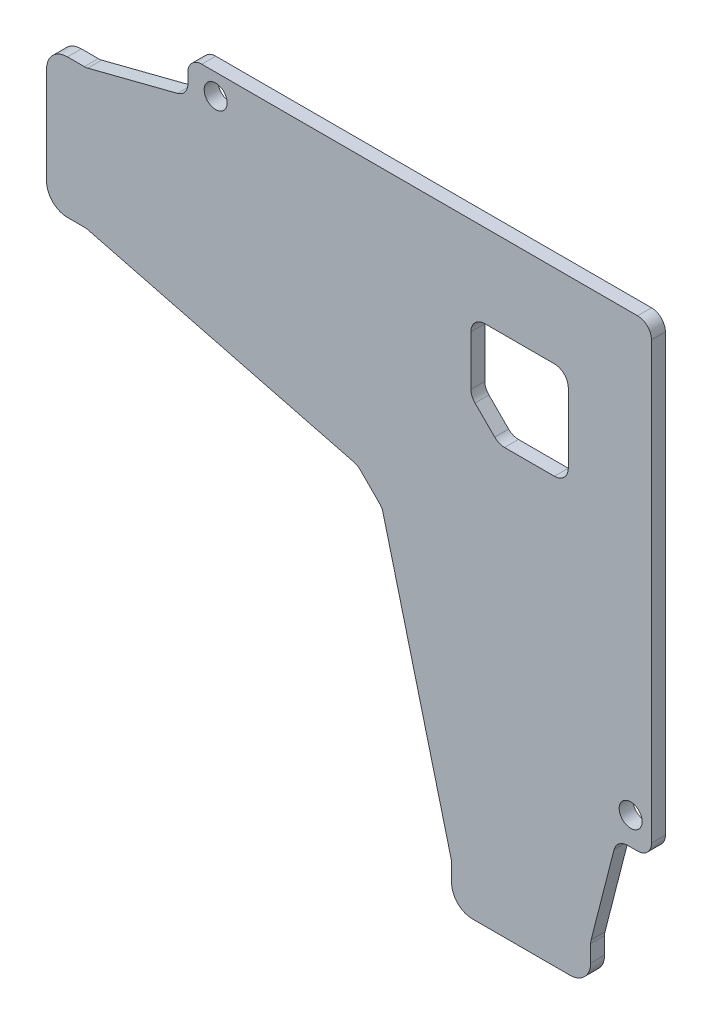
SolidWorks part; units mm, degrees
ref_plane "Front Plane" through (0, 0, 0) normal (0, 0, 1) x (1, 0, 0)
ref_plane "Top Plane" through (0, 0, 0) normal (0, 1, 0) x (1, 0, 0)
ref_plane "Right Plane" through (0, 0, 0) normal (1, 0, 0) x (0, 0, -1)
sketch "Sketch1" plane through (0, 0, 0) normal (0, 0, 1) x (1, 0, 0)
  line L0 (-86, -7.75) -> (-86, -27.75)
  line L1 (-27.75, -86) -> (-7.75, -86)
  line L2 (-86, -7.75) -> (-95.5, -7.75) construction
  line L3 (-86, -27.75) -> (-80.5674, -27.75)
  line L4 (-27.75, -86) -> (-27.75, -95.5) construction
  line L5 (-7.75, -86) -> (-7.75, -80.5674)
  line L23 (-10.25, -92) -> (-10.25, -95.5)
  line L24 (-10.25, -95.5) -> (-7.75, -95.5)
  line L25 (-7.75, -95.5) -> (-7.75, -80.5674)
  line L26 (-7.6874, -80.0709) -> (-4.3853, -67.1846)
  line L27 (-2.4479, -65.6811) -> (-1, -65.6811)
  line L28 (1, -63.6811) -> (1, -1)
  line L29 (-1, 1) -> (-63.6811, 1)
  line L30 (-65.6811, -1) -> (-65.6811, -2.4479)
  line L31 (-67.1846, -4.3853) -> (-80.0709, -7.6874)
  line L32 (-80.5674, -7.75) -> (-95.5, -7.75)
  line L33 (-95.5, -7.75) -> (-95.5, -10.25)
  line L34 (-95.5, -10.25) -> (-92, -10.25)
  line L35 (-90, -12.25) -> (-90, -23.25)
  line L36 (-92, -25.25) -> (-95.5, -25.25)
  line L37 (-95.5, -25.25) -> (-95.5, -27.75)
  line L38 (-95.5, -27.75) -> (-80.5674, -27.75)
  line L39 (-80.0709, -27.8126) -> (-41.8142, -37.6159)
  line L40 (-40.8965, -38.1391) -> (-38.1391, -40.8965)
  line L41 (-37.6159, -41.8142) -> (-27.8126, -80.0709)
  line L42 (-27.75, -80.5674) -> (-27.75, -95.5)
  line L43 (-27.75, -95.5) -> (-25.25, -95.5)
  line L44 (-25.25, -95.5) -> (-25.25, -92)
  line L45 (-23.25, -90) -> (-12.25, -90)
  line L46 (-10.25, -92) -> (-10.25, -95.5) construction
  line L47 (-10.25, -95.5) -> (-7.75, -95.5) construction
  line L48 (-7.75, -95.5) -> (-7.75, -86) construction
  line L49 (-7.6874, -80.0709) -> (-4.3853, -67.1846)
  line L50 (-2.4479, -65.6811) -> (-1, -65.6811)
  line L51 (1, -63.6811) -> (1, -1)
  line L52 (-1, 1) -> (-63.6811, 1)
  line L53 (-65.6811, -1) -> (-65.6811, -2.4479)
  line L54 (-67.1846, -4.3853) -> (-80.0709, -7.6874)
  line L55 (-80.5674, -7.75) -> (-86, -7.75)
  line L56 (-95.5, -7.75) -> (-95.5, -10.25) construction
  line L57 (-95.5, -10.25) -> (-92, -10.25) construction
  line L58 (-90, -12.25) -> (-90, -23.25) construction
  line L59 (-92, -25.25) -> (-95.5, -25.25) construction
  line L60 (-95.5, -25.25) -> (-95.5, -27.75) construction
  line L61 (-95.5, -27.75) -> (-86, -27.75) construction
  line L62 (-80.0709, -27.8126) -> (-41.8142, -37.6159)
  line L63 (-40.8965, -38.1391) -> (-38.1391, -40.8965)
  line L64 (-37.6159, -41.8142) -> (-27.8126, -80.0709)
  line L65 (-27.75, -80.5674) -> (-27.75, -86)
  line L66 (-27.75, -95.5) -> (-25.25, -95.5) construction
  line L67 (-25.25, -95.5) -> (-25.25, -92) construction
  line L68 (-23.25, -90) -> (-12.25, -90) construction
  arc A15 (-7.6874, -80.0709) -> (-7.75, -80.5674) centre (-5.75, -80.5674) ccw
  arc A16 (-2.4479, -65.6811) -> (-4.3853, -67.1846) centre (-2.4479, -67.6811) ccw
  arc A17 (-1, -65.6811) -> (1, -63.6811) centre (-1, -63.6811) ccw
  arc A18 (1, -1) -> (-1, 1) centre (-1, -1) ccw
  arc A19 (-63.6811, 1) -> (-65.6811, -1) centre (-63.6811, -1) ccw
  arc A20 (-67.1846, -4.3853) -> (-65.6811, -2.4479) centre (-67.6811, -2.4479) ccw
  arc A21 (-80.5674, -7.75) -> (-80.0709, -7.6874) centre (-80.5674, -5.75) ccw
  arc A22 (-90, -12.25) -> (-92, -10.25) centre (-92, -12.25) ccw
  arc A23 (-92, -25.25) -> (-90, -23.25) centre (-92, -23.25) ccw
  arc A24 (-80.0709, -27.8126) -> (-80.5674, -27.75) centre (-80.5674, -29.75) ccw
  arc A25 (-40.8965, -38.1391) -> (-41.8142, -37.6159) centre (-42.3107, -39.5533) ccw
  arc A26 (-37.6159, -41.8142) -> (-38.1391, -40.8965) centre (-39.5533, -42.3107) ccw
  arc A27 (-27.75, -80.5674) -> (-27.8126, -80.0709) centre (-29.75, -80.5674) ccw
  arc A28 (-23.25, -90) -> (-25.25, -92) centre (-23.25, -92) ccw
  arc A29 (-10.25, -92) -> (-12.25, -90) centre (-12.25, -92) ccw
  arc A30 (-7.6874, -80.0709) -> (-7.75, -80.5674) centre (-5.75, -80.5674) ccw
  arc A31 (-2.4479, -65.6811) -> (-4.3853, -67.1846) centre (-2.4479, -67.6811) ccw
  arc A32 (-1, -65.6811) -> (1, -63.6811) centre (-1, -63.6811) ccw
  arc A33 (1, -1) -> (-1, 1) centre (-1, -1) ccw
  arc A34 (-63.6811, 1) -> (-65.6811, -1) centre (-63.6811, -1) ccw
  arc A35 (-67.1846, -4.3853) -> (-65.6811, -2.4479) centre (-67.6811, -2.4479) ccw
  arc A36 (-80.5674, -7.75) -> (-80.0709, -7.6874) centre (-80.5674, -5.75) ccw
  arc A37 (-90, -12.25) -> (-92, -10.25) centre (-92, -12.25) ccw construction
  arc A38 (-92, -25.25) -> (-90, -23.25) centre (-92, -23.25) ccw construction
  arc A39 (-80.0709, -27.8126) -> (-80.5674, -27.75) centre (-80.5674, -29.75) ccw
  arc A40 (-40.8965, -38.1391) -> (-41.8142, -37.6159) centre (-42.3107, -39.5533) ccw
  arc A41 (-37.6159, -41.8142) -> (-38.1391, -40.8965) centre (-39.5533, -42.3107) ccw
  arc A42 (-27.75, -80.5674) -> (-27.8126, -80.0709) centre (-29.75, -80.5674) ccw
  arc A43 (-23.25, -90) -> (-25.25, -92) centre (-23.25, -92) ccw construction
  arc A44 (-10.25, -92) -> (-12.25, -90) centre (-12.25, -92) ccw construction
  dimension "D2" = 4
  dimension "D3" = 4
  dimension "D1" = 0
sketch "Sketch2" plane through (0, 0, 0) normal (0, 0, 1) x (1, 0, 0)
  circle A0 centre (-61.6811, -2) radius 1.65 construction
  circle A1 centre (-2, -61.6811) radius 1.65 construction
  circle A2 centre (-61.6811, -2) radius 1.65
  circle A3 centre (-2, -61.6811) radius 1.65
sketch "Sketch4" plane through (0, 0, 0) normal (0, 0, 1) x (1, 0, 0)
  line L0 (-24.9687, -12.9687) -> (-24.9687, -20.1403) construction
  line L1 (-12.9687, -10.9687) -> (-22.9687, -10.9687) construction
  line L2 (-10.9687, -22.9687) -> (-10.9687, -12.9687) construction
  line L3 (-20.1403, -24.9687) -> (-12.9687, -24.9687) construction
  line L4 (-24.9687, -12.9687) -> (-24.9687, -20.1403)
  line L5 (-12.9687, -10.9687) -> (-22.9687, -10.9687)
  line L6 (-10.9687, -22.9687) -> (-10.9687, -12.9687)
  line L7 (-20.1403, -24.9687) -> (-12.9687, -24.9687)
  line L8 (-21.5545, -24.3829) -> (-24.3829, -21.5545) construction
  line L9 (-21.5545, -24.3829) -> (-24.3829, -21.5545)
  arc A0 (-24.9687, -20.1403) -> (-24.3829, -21.5545) centre (-22.9687, -20.1403) ccw construction
  arc A1 (-21.5545, -24.3829) -> (-20.1403, -24.9687) centre (-20.1403, -22.9687) ccw construction
  arc A2 (-22.9687, -10.9687) -> (-24.9687, -12.9687) centre (-22.9687, -12.9687) ccw construction
  arc A3 (-10.9687, -12.9687) -> (-12.9687, -10.9687) centre (-12.9687, -12.9687) ccw construction
  arc A4 (-12.9687, -24.9687) -> (-10.9687, -22.9687) centre (-12.9687, -22.9687) ccw construction
  arc A5 (-24.9687, -20.1403) -> (-24.3829, -21.5545) centre (-22.9687, -20.1403) ccw
  arc A6 (-22.9687, -10.9687) -> (-24.9687, -12.9687) centre (-22.9687, -12.9687) ccw
  arc A7 (-10.9687, -12.9687) -> (-12.9687, -10.9687) centre (-12.9687, -12.9687) ccw
  arc A8 (-12.9687, -24.9687) -> (-10.9687, -22.9687) centre (-12.9687, -22.9687) ccw
  arc A9 (-21.5545, -24.3829) -> (-20.1403, -24.9687) centre (-20.1403, -22.9687) ccw
extrude "Boss-Extrude1" add sketch "Sketch1" along normal blind 2
extrude "Cut-Extrude2" cut sketch "Sketch4" along normal through all
sketch "Sketch5" plane through (0, 0, 0) normal (0, 0, 1) x (1, 0, 0)
  line L0 (-78.4965, -9.8647) -> (-46.0979, -1.5626) construction
  line L1 (-78.4965, -9.8647) -> (-46.0979, -1.5626) construction
  line L2 (-80, -11.8021) -> (-80, -23.6979) construction
  line L3 (-40.5305, -35.3641) -> (-78.4965, -25.6353) construction
  line L4 (-35.8872, -39.6128) -> (-39.6128, -35.8872) construction
  line L5 (-25.6353, -78.4965) -> (-35.3641, -40.5305) construction
  line L6 (-23.6979, -80) -> (-11.8021, -80) construction
  line L7 (-1.5626, -46.0979) -> (-9.8647, -78.4965) construction
  line L8 (-1.5, -3.5) -> (-1.5, -45.6015) construction
  line L9 (-45.6015, -1.5) -> (-3.5, -1.5) construction
  line L10 (-80, -11.8021) -> (-80, -23.6979) construction
  line L11 (-40.5305, -35.3641) -> (-78.4965, -25.6353) construction
  line L12 (-35.8872, -39.6128) -> (-39.6128, -35.8872) construction
  line L13 (-25.6353, -78.4965) -> (-35.3641, -40.5305) construction
  line L14 (-23.6979, -80) -> (-11.8021, -80) construction
  line L15 (-1.5626, -46.0979) -> (-9.8647, -78.4965) construction
  line L16 (-1.5, -3.5) -> (-1.5, -45.6015) construction
  line L17 (-45.6015, -1.5) -> (-3.5, -1.5) construction
  line L18 (-78.4716, -9.9616) -> (-46.0731, -1.6595)
  line L19 (-45.6015, -1.6) -> (-3.5, -1.6)
  line L20 (-1.6, -3.5) -> (-1.6, -45.6015)
  line L21 (-1.6595, -46.0731) -> (-9.9616, -78.4716)
  line L22 (-23.6979, -79.9) -> (-11.8021, -79.9)
  line L23 (-25.5384, -78.4716) -> (-35.2672, -40.5057)
  line L24 (-35.8165, -39.542) -> (-39.542, -35.8165)
  line L25 (-40.5057, -35.2672) -> (-78.4716, -25.5384)
  line L26 (-79.9, -11.8021) -> (-79.9, -23.6979)
  line L27 (-77.8, -11.9573) -> (-77.8, -23.5427)
  line L28 (-39.9844, -33.2329) -> (-77.8, -23.5427)
  line L29 (-34.3316, -38.0571) -> (-38.0571, -34.3316)
  line L30 (-23.5427, -77.8) -> (-33.2329, -39.9844)
  line L31 (-23.5427, -77.8) -> (-11.9573, -77.8)
  line L32 (-3.7, -45.5763) -> (-11.9573, -77.8)
  line L33 (-3.7, -3.7) -> (-3.7, -45.5763)
  line L34 (-45.5763, -3.7) -> (-3.7, -3.7)
  line L35 (-77.8, -11.9573) -> (-45.5763, -3.7)
  arc A0 (-78.4965, -9.8647) -> (-80, -11.8021) centre (-78, -11.8021) ccw construction
  arc A1 (-80, -23.6979) -> (-78.4965, -25.6353) centre (-78, -23.6979) ccw construction
  arc A2 (-39.6128, -35.8872) -> (-40.5305, -35.3641) centre (-41.027, -37.3015) ccw construction
  arc A3 (-25.6353, -78.4965) -> (-23.6979, -80) centre (-23.6979, -78) ccw construction
  arc A4 (-11.8021, -80) -> (-9.8647, -78.4965) centre (-11.8021, -78) ccw construction
  arc A5 (-1.5626, -46.0979) -> (-1.5, -45.6015) centre (-3.5, -45.6015) ccw construction
  arc A6 (-1.5, -3.5) -> (-3.5, -1.5) centre (-3.5, -3.5) ccw construction
  arc A7 (-45.6015, -1.5) -> (-46.0979, -1.5626) centre (-45.6015, -3.5) ccw construction
  arc A8 (-78.4965, -9.8647) -> (-80, -11.8021) centre (-78, -11.8021) ccw construction
  arc A9 (-80, -23.6979) -> (-78.4965, -25.6353) centre (-78, -23.6979) ccw construction
  arc A10 (-39.6128, -35.8872) -> (-40.5305, -35.3641) centre (-41.027, -37.3015) ccw construction
  arc A11 (-25.6353, -78.4965) -> (-23.6979, -80) centre (-23.6979, -78) ccw construction
  arc A12 (-11.8021, -80) -> (-9.8647, -78.4965) centre (-11.8021, -78) ccw construction
  arc A13 (-1.5626, -46.0979) -> (-1.5, -45.6015) centre (-3.5, -45.6015) ccw construction
  arc A14 (-1.5, -3.5) -> (-3.5, -1.5) centre (-3.5, -3.5) ccw construction
  arc A15 (-45.6015, -1.5) -> (-46.0979, -1.5626) centre (-45.6015, -3.5) ccw construction
  arc A16 (-45.6015, -1.6) -> (-46.0731, -1.6595) centre (-45.6015, -3.5) ccw
  arc A17 (-1.6, -3.5) -> (-3.5, -1.6) centre (-3.5, -3.5) ccw
  arc A18 (-1.6595, -46.0731) -> (-1.6, -45.6015) centre (-3.5, -45.6015) ccw
  arc A19 (-11.8021, -79.9) -> (-9.9616, -78.4716) centre (-11.8021, -78) ccw
  arc A20 (-25.5384, -78.4716) -> (-23.6979, -79.9) centre (-23.6979, -78) ccw
  arc A21 (-35.2672, -40.5057) -> (-35.8165, -39.542) centre (-37.3015, -41.027) ccw
  arc A22 (-39.542, -35.8165) -> (-40.5057, -35.2672) centre (-41.027, -37.3015) ccw
  arc A23 (-79.9, -23.6979) -> (-78.4716, -25.5384) centre (-78, -23.6979) ccw
  arc A24 (-35.3641, -40.5305) -> (-35.8872, -39.6128) centre (-37.3015, -41.027) ccw construction
  arc A25 (-35.3641, -40.5305) -> (-35.8872, -39.6128) centre (-37.3015, -41.027) ccw construction
  arc A26 (-78.4716, -9.9616) -> (-79.9, -11.8021) centre (-78, -11.8021) ccw
  arc A27 (-77.8, -23.5427) -> (-77.8, -23.5427) centre (-77.8, -23.5427) ccw
  arc A28 (-38.0571, -34.3316) -> (-39.9844, -33.2329) centre (-41.027, -37.3015) ccw
  arc A29 (-33.2329, -39.9844) -> (-34.3316, -38.0571) centre (-37.3015, -41.027) ccw
  arc A30 (-23.5427, -77.8) -> (-23.5427, -77.8) centre (-23.5427, -77.8) ccw
  arc A31 (-11.9573, -77.8) -> (-11.9573, -77.8) centre (-11.9573, -77.8) ccw
  arc A32 (-3.7, -45.5763) -> (-3.7, -45.5763) centre (-3.7, -45.5763) ccw
  arc A33 (-3.7, -3.7) -> (-3.7, -3.7) centre (-3.7, -3.7) ccw
  arc A34 (-45.5763, -3.7) -> (-45.5763, -3.7) centre (-45.5763, -3.7) ccw
  arc A35 (-77.8, -11.9573) -> (-77.8, -11.9573) centre (-77.8, -11.9573) ccw
  dimension "D1" = 0.1
  dimension "D2" = 2.2
extrude "Boss-Extrude2" add sketch "Sketch5" against normal blind 1.2
chamfer "Chamfer1" distance 1.2 angle 45 11 edges at (-28.3878, -58.8922, 0) (-33.6527, -38.9469, 0) (-36.1944, -36.1944, 0) (-38.9469, -33.6527, 0) (-17.75, -77.8, 0) (-7.8287, -61.6881, 0) (-3.7, -24.6381, 0) (-24.6381, -3.7, 0) (-61.6881, -7.8287, 0) (-77.8, -17.75, 0) (-58.8922, -28.3878, 0)
extrude "Cut-Extrude3" cut sketch "Sketch2" along normal through all
fillet "Fillet1" radius 3 4 edges at (-27.75, -86, 1) (-7.75, -86, 1) (-86, -7.75, 1) (-86, -27.75, 1)
